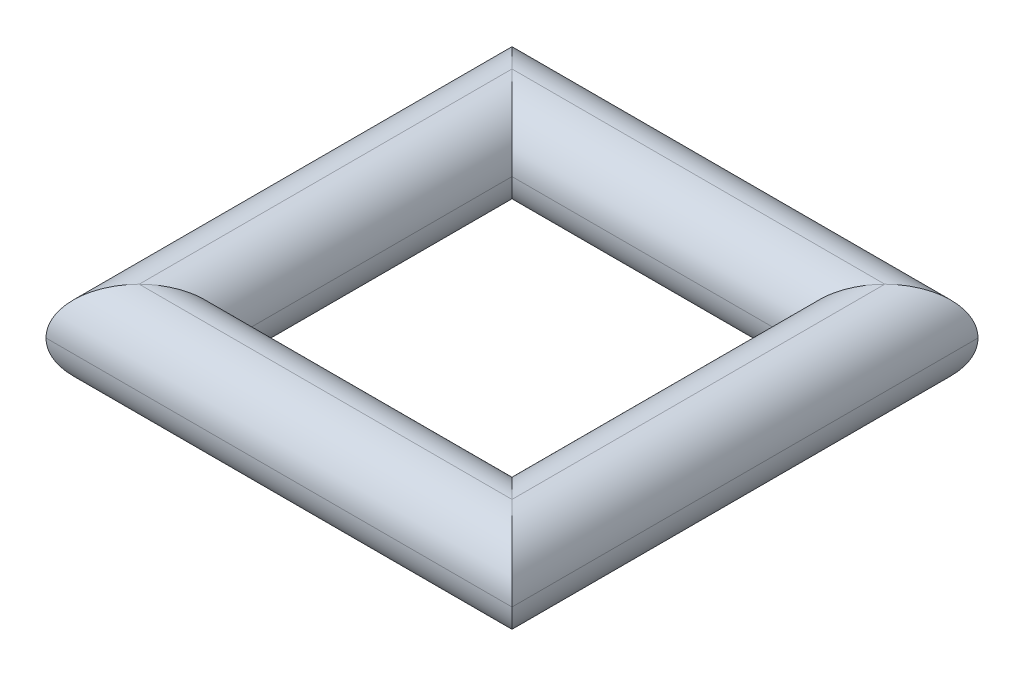
SolidWorks part; units mm, degrees
ref_plane "Front Plane" through (0, 0, 0) normal (0, 0, 1) x (1, 0, 0)
ref_plane "Top Plane" through (0, 0, 0) normal (0, 1, 0) x (1, 0, 0)
ref_plane "Right Plane" through (0, 0, 0) normal (1, 0, 0) x (0, 0, -1)
sketch "Sketch1" plane through (0, 0, 0) normal (0, 1, 0) x (1, 0, 0)
  line L1 (-33.0189, 25.4717) -> (-8.0189, 25.4717)
  line L2 (-33.0189, 25.4717) -> (-33.0189, 0.4717)
  line L3 (-33.0189, 0.4717) -> (-8.0189, 0.4717)
  line L4 (-8.0189, 25.4717) -> (-8.0189, 0.4717)
  dimension "D1" = 25
  dimension "D2" = 25
extrude "Boss-Extrude1" add sketch "Sketch1" along normal blind 5 contours L2 L3 L4 L1
sketch "Sketch2" plane through (0, 5, 0) normal (0, 1, 0) x (1, 0, 0)
  line L0 (-33.0189, 25.4717) -> (-8.0189, 25.4717) construction
  line L1 (-28.0189, 20.4717) -> (-13.0189, 20.4717)
  line L2 (-28.0189, 20.4717) -> (-28.0189, 5.4717)
  line L3 (-28.0189, 5.4717) -> (-13.0189, 5.4717)
  line L4 (-13.0189, 20.4717) -> (-13.0189, 5.4717)
  line L5 (-33.0189, 25.4717) -> (-33.0189, 0.4717) construction
  line L6 (-33.0189, 0.4717) -> (-8.0189, 0.4717) construction
  line L7 (-8.0189, 25.4717) -> (-8.0189, 0.4717) construction
  dimension "D1" = 5
  dimension "D2" = 5
  dimension "D3" = 5
  dimension "D4" = 5
extrude "Cut-Extrude1" cut sketch "Sketch2" against normal blind 5
fillet "Fillet1" radius 2.5 8 edges at (-8.0189, 5, -12.9717) (-20.5189, 5, -0.4717) (-33.0189, 5, -12.9717) (-20.5189, 5, -25.4717) (-13.0189, 5, -12.9717) (-20.5189, 5, -20.4717) (-28.0189, 5, -12.9717) (-20.5189, 5, -5.4717)
fillet "Fillet2" radius 2.5 8 edges at (-33.0189, 0, -12.9717) (-20.5189, 0, -0.4717) (-8.0189, 0, -12.9717) (-20.5189, 0, -25.4717) (-20.5189, 0, -20.4717) (-13.0189, 0, -12.9717) (-20.5189, 0, -5.4717) (-28.0189, 0, -12.9717)
